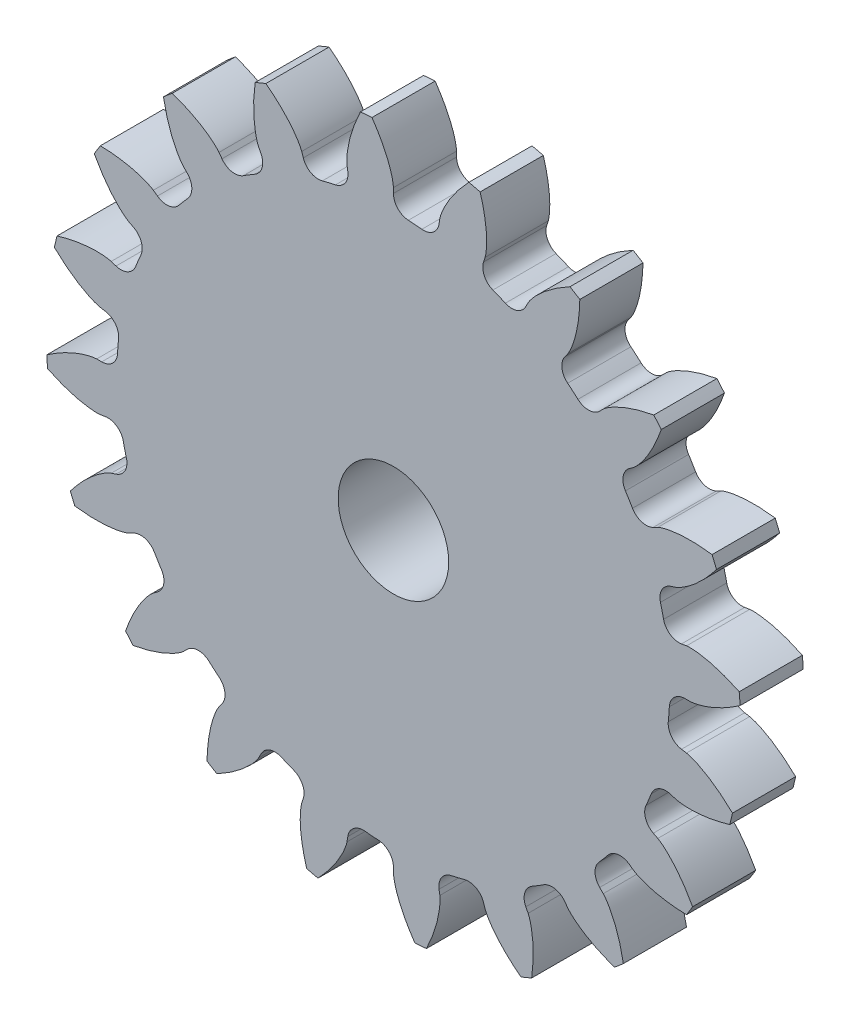
SolidWorks part; units mm, degrees
ref_plane "Plan de face" through (0, 0, 0) normal (0, 0, 1) x (1, 0, 0)
ref_plane "Plan de dessus" through (0, 0, 0) normal (0, 1, 0) x (1, 0, 0)
ref_plane "Plan de droite" through (0, 0, 0) normal (1, 0, 0) x (0, 0, -1)
sketch "Esquisse1" plane through (0, 0, 0) normal (0, 0, 1) x (1, 0, 0)
  line L0 (0, 0) -> (14, 0) construction
  line L1 (4, -8.4784) -> (4, 14.4842) construction
  line L2 (0.7385, -8.9609) -> (9.5058, 15.1269) construction
  line L3 (0, 0) -> (7.629, 1.5175) construction
  line L4 (3.4727, 1.4384) -> (2.9669, 1.2289)
  line L5 (3.2113, 0) -> (3.7588, 0)
  circle A0 centre (0, 0) radius 4 construction
  circle A1 centre (14, 0) radius 10 construction
  circle A2 centre (0, 0) radius 1.75
  circle A3 centre (0, 0) radius 3.7588 construction
  arc A4 (2.3485, 1.4307) -> (2.7173, -0.4231) centre (0, 0) ccw
  arc A5 (4.9384, 0.7823) -> (4.8619, 1.1671) centre (0, 0) ccw
  circle A6 centre (0, 0) radius 5 construction
  arc A7 (2.9669, 1.2289) -> (2.3485, 1.4307) centre (2.7755, 1.6909) cw
  arc A8 (3.2113, 0) -> (2.7173, -0.4231) centre (3.2113, -0.5) ccw
  spline S0 degree 4 poles (3.7588, 0) (3.7615, 0.0001) (3.7693, 0.0004) (3.784, 0.0018) (3.8079, 0.005) (3.8381, 0.0107) (3.8769, 0.0197) (3.9222, 0.0324) (3.9714, 0.0487) (4.0242, 0.0688) (4.0763, 0.0909) (4.1275, 0.115) (4.1779, 0.1406) (4.2382, 0.1737) (4.3091, 0.2162) (4.3902, 0.2697) (4.4797, 0.3351) (4.5682, 0.4064) (4.6528, 0.4804) (4.7355, 0.5595) (4.8133, 0.639) (4.8749, 0.7079) (4.9141, 0.7532) (4.9353, 0.7785) (4.9384, 0.7823) knots 0 0 0 0 0 0.005377 0.015084 0.028532 0.04661 0.064855 0.092111 0.119476 0.146842 0.174209 0.201575 0.228941 0.256307 0.307035 0.361767 0.4165 0.471232 0.525964 0.580697 0.635429 0.690161 0.699806 0.699806 0.699806 0.699806 0.699806
  spline S2 degree 4 poles (3.4727, 1.4384) (3.4752, 1.4394) (3.4826, 1.4421) (3.4967, 1.4464) (3.52, 1.4526) (3.5501, 1.4589) (3.5893, 1.4655) (3.636, 1.471) (3.6877, 1.4748) (3.7442, 1.4765) (3.8008, 1.4759) (3.8573, 1.4733) (3.9137, 1.4689) (3.982, 1.4614) (4.0639, 1.4493) (4.1592, 1.4308) (4.267, 1.4047) (4.376, 1.3727) (4.4825, 1.3367) (4.5891, 1.2953) (4.6914, 1.2516) (4.7747, 1.2116) (4.8283, 1.1847) (4.8575, 1.1694) (4.8619, 1.1671) knots 0 0 0 0 0 0.005377 0.015084 0.028532 0.04661 0.064855 0.092111 0.119476 0.146842 0.174209 0.201575 0.228941 0.256307 0.307035 0.361767 0.4165 0.471232 0.525964 0.580697 0.635429 0.690161 0.699806 0.699806 0.699806 0.699806 0.699806
  point P9 (3.5321, -1.2856)
  point P12 (4, 0)
  dimension "Dp" = 8
  dimension "D3" = 20
  dimension "Db" = 7.5175
  dimension "Di" = 5.5
  dimension "D2" = 3.5
  dimension "Da" = 10
  dimension "D5" = 0.5
  dimension "D4" = 20
  dimension "angle" = 11.25
  dimension "D1" = 14
extrude "Boss.-Extru.1" add sketch "Esquisse1" along normal blind 2
pattern_circular "Répétition circulaire1" count 8 over 360 about axis through (0, 0, 2) along (0, 0, 1) of "Boss.-Extru.1"
sketch "Esquisse2" plane through (0, 0, 2) normal (0, 0, 1) x (1, 0, 0)
  line L0 (10, 0) -> (10, 32.6573) construction
  line L1 (44.2221, 0) -> (-0.014, 0) construction
  line L2 (-3.3116, -36.5733) -> (21.4095, 31.3474) construction
  line L3 (0, 0) -> (30.9675, 2.4372) construction
  line L4 (9.3969, 0) -> (9.2365, 0)
  line L5 (9.2812, 1.47) -> (9.1228, 1.4449)
  circle A0 centre (0, 0) radius 1.75
  arc A1 (8.5556, 1.834) -> (8.7372, -0.473) centre (0, 0) ccw
  circle A2 centre (0, 0) radius 9.3969 construction
  circle A3 centre (0, 0) radius 10 construction
  arc A4 (10.979, 0.68) -> (10.9502, 1.0459) centre (0, 0) ccw
  arc A5 (9.1228, 1.4449) -> (8.5556, 1.834) centre (9.0445, 1.9387) cw
  arc A6 (9.2365, 0) -> (8.7372, -0.473) centre (9.2365, -0.5) ccw
  spline S0 degree 4 poles (9.3969, 0) (9.3999, 0) (9.4081, 0.0003) (9.4236, 0.0012) (9.449, 0.0035) (9.4812, 0.0073) (9.5228, 0.0135) (9.5717, 0.0224) (9.6252, 0.0336) (9.6833, 0.0476) (9.741, 0.0631) (9.7984, 0.0799) (9.8553, 0.0979) (9.9241, 0.1212) (10.0061, 0.1511) (10.1014, 0.1892) (10.2088, 0.2358) (10.3173, 0.287) (10.4233, 0.3405) (10.5295, 0.398) (10.6316, 0.4561) (10.7366, 0.52) (10.832, 0.5801) (10.9108, 0.6331) (10.9564, 0.6643) (10.979, 0.68) knots 0 0 0 0 0 0.005377 0.015084 0.028532 0.04661 0.064855 0.092111 0.119476 0.146842 0.174209 0.201575 0.228941 0.256307 0.307035 0.361767 0.4165 0.471232 0.525964 0.580697 0.635429 0.690161 0.744894 0.797218 0.797218 0.797218 0.797218 0.797218
  spline S2 degree 4 poles (9.2812, 1.47) (9.2841, 1.4704) (9.2923, 1.4715) (9.3078, 1.473) (9.3332, 1.4747) (9.3657, 1.4759) (9.4077, 1.4763) (9.4574, 1.4752) (9.512, 1.4725) (9.5715, 1.4678) (9.631, 1.4615) (9.6902, 1.4539) (9.7493, 1.445) (9.8208, 1.4328) (9.9066, 1.416) (10.0066, 1.3934) (10.12, 1.3641) (10.2352, 1.3305) (10.3483, 1.2943) (10.4622, 1.2541) (10.5721, 1.2127) (10.6858, 1.166) (10.7894, 1.1216) (10.8755, 1.0815) (10.9255, 1.0578) (10.9502, 1.0459) knots 0 0 0 0 0 0.005377 0.015084 0.028532 0.04661 0.064855 0.092111 0.119476 0.146842 0.174209 0.201575 0.228941 0.256307 0.307035 0.361767 0.4165 0.471232 0.525964 0.580697 0.635429 0.690161 0.744894 0.797218 0.797218 0.797218 0.797218 0.797218
  point P10 (10, 0)
  dimension "Dp" = 20
  dimension "Di" = 17.5
  dimension "Db" = 18.7939
  dimension "D3" = 22
  dimension "D4" = 0.5
  dimension "D1" = 20
  dimension "D2" = 4.5
extrude "Boss.-Extru.2" add sketch "Esquisse2" along normal blind 2
pattern_circular "Répétition circulaire2" count 20 over 360 about axis through (0, 0, 2) along (0, 0, 1) of "Boss.-Extru.2"
equation "\"M\"= 1"
equation "\"Z\"= \"Dp@Esquisse1\" / \"M\""
equation "\"t\"= 1.25 * \"M\""
equation "\"e\"= \"M\" * pi / 2"
equation "\"Di@Esquisse1\" = \"Dp@Esquisse1\" -  ( 2 * \"t\" ) "
equation "\"Da@Esquisse1\"=\"Dp@Esquisse1\" + 2 * \"M\""
equation "\"angle@Esquisse1\"=360/\"Z\"/4"
equation "\"D1@Répétition circulaire1\"=\"Z\""
equation "\"Di@Esquisse2\"=\"Dp@Esquisse2\" -  ( 2 * \"t\" )"
equation "\"D3@Esquisse2\"=\"Dp@Esquisse2\" + 2 * \"M\""
equation "\"D2@Esquisse2\"=90/20"
